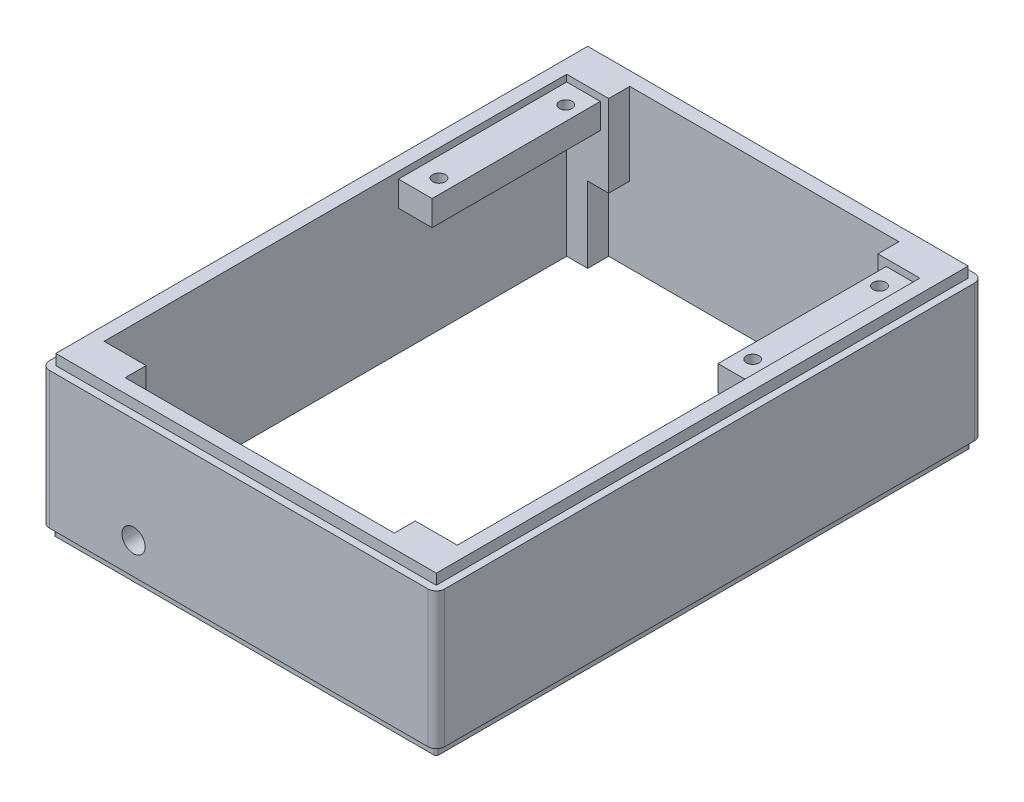
SolidWorks part; units mm, degrees
ref_plane "Front Plane" through (0, 0, 0) normal (0, 0, 1) x (1, 0, 0)
ref_plane "Top Plane" through (0, 0, 0) normal (0, 1, 0) x (1, 0, 0)
ref_plane "Right Plane" through (0, 0, 0) normal (1, 0, 0) x (0, 0, -1)
ref_plane "Plane1" through (0, 0, 0) normal (0, -1, 0) x (1, 0, 0)
sketch "Sketch1" plane through (0, 0, 0) normal (0, -1, 0) x (1, 0, 0)
  line L0 (94, 0) -> (0, 0)
  line L1 (0, 0) -> (0, -130)
  line L2 (0, -130) -> (94, -130)
  line L3 (94, -130) -> (94, 0)
extrude "Boss-Extrude1" add sketch "Sketch1" against normal blind 35
sketch "Sketch2" plane through (0, 35, 0) normal (0, 1, 0) x (-1, 0, 0)
  line L0 (-1.75, -128.25) -> (-92.25, -128.25)
  line L1 (-92.25, -128.25) -> (-92.25, -1.75)
  line L2 (-92.25, -1.75) -> (-1.75, -1.75)
  line L3 (-1.75, -1.75) -> (-1.75, -128.25)
extrude "Boss-Extrude2" add sketch "Sketch2" along normal blind 2.5
sketch "Sketch3" plane through (0, 37.5, 0) normal (0, 1, 0) x (-1, 0, 0)
  line L1 (-83, -120) -> (-79, -120)
  line L2 (-79, -120) -> (-79, -125)
  line L3 (-79, -125) -> (-15, -125)
  line L4 (-15, -125) -> (-15, -120)
  line L5 (-15, -120) -> (-5, -120)
  line L6 (-5, -120) -> (-5, -10)
  line L7 (-5, -10) -> (-15, -10)
  line L8 (-15, -10) -> (-15, -5)
  line L9 (-15, -5) -> (-79, -5)
  line L10 (-79, -5) -> (-79, -10)
  line L11 (-79, -10) -> (-89, -10)
  line L12 (-89, -10) -> (-89, -96)
  line L14 (-83, -120) -> (-89, -120)
  line L15 (-89, -120) -> (-89, -96)
extrude "Cut-Extrude1" cut sketch "Sketch3" against normal through all
sketch "Sketch4" plane through (0, 0, -10) normal (0, 0, -1) x (-1, 0, 0)
  line L0 (-15, 0) -> (-10, 0)
  line L1 (-10, 0) -> (-10, 18)
  line L2 (-10, 18) -> (-15, 18)
  line L3 (-15, 18) -> (-15, 0)
extrude "Cut-Extrude2" cut sketch "Sketch4" against normal blind 5
ref_plane "Plane2" through (0, 33.5, 0) normal (0, 1, 0) x (1, 0, 0)
ref_plane "Plane3" through (0, 31.5, 0) normal (0, -1, 0) x (1, 0, 0)
sketch "Sketch9" plane through (0, 0, -10) normal (0, 0, -1) x (-1, 0, 0)
  line L0 (-79, 18) -> (-84, 18)
  line L1 (-84, 18) -> (-84, 0)
  line L2 (-84, 0) -> (-79, 0)
  line L3 (-79, 0) -> (-79, 18)
extrude "Cut-Extrude6" cut sketch "Sketch9" against normal blind 5
sketch "Sketch11" plane through (0, 0, 0) normal (0, -1, 0) x (1, 0, 0)
  line L0 (15, -125) -> (15, -120)
  line L1 (15, -120) -> (10, -120)
  line L2 (10, -120) -> (10, -125)
  line L3 (10, -125) -> (15, -125)
extrude "Cut-Extrude8" cut sketch "Sketch11" against normal blind 18
sketch "Sketch12" plane through (0, 0, -120) normal (0, 0, 1) x (1, 0, 0)
  line L0 (79, 0) -> (84, 0)
  line L1 (84, 0) -> (84, 18)
  line L2 (84, 18) -> (79, 18)
  line L3 (79, 18) -> (79, 0)
extrude "Cut-Extrude9" cut sketch "Sketch12" against normal blind 5
hole_wizard "Ø5.5 (5.5) Diameter Hole1" positions "Sketch14" profile "Sketch13" hole size "Ø5.5" standard "ANSI Metric" end condition through all
sketch "Sketch14" plane through (0, 0, -5) normal (0, 0, -1) x (-1, 0, 0)
  point P0 (-22, 10)
sketch "Sketch13" plane through (22, 10, -5) normal (1, 0, 0) x (0, 1, 0)
  line L0 (0, 0) -> (0, 5)
  line L1 (0, 5) -> (2.75, 5)
  line L2 (2.75, 5) -> (2.75, 0)
  line L5 (2.75, 0) -> (0, 0)
  line L11 (0, -6.35) -> (0, 107.95) construction
  dimension "Thru Hole Dia." = 5.5
  dimension "Thru Hole Depth" = 5
ref_plane "Plane4" through (0, 29.5, 0) normal (0, -1, 0) x (1, 0, 0)
fillet "Fillet1" radius 2 4 edges at (0, 17.5, -130) (94, 17.5, -130) (0, 17.5, 0) (94, 17.5, 0) tangent propagation no
sketch "Sketch16" plane through (0, 0, 0) normal (0, -1, 0) x (1, 0, 0)
  line L4 (1.5, -2) -> (1.5, -128)
  line L5 (2, -128.5) -> (92, -128.5)
  line L6 (92.5, -128) -> (92.5, -2)
  line L7 (92, -1.5) -> (2, -1.5)
  line L8 (0, -2) -> (0, -128)
  line L9 (2, -130) -> (92, -130)
  line L10 (94, -128) -> (94, -2)
  line L11 (92, 0) -> (2, 0)
  line L12 (0, -2) -> (0, -128)
  line L13 (2, -130) -> (92, -130)
  line L14 (94, -128) -> (94, -2)
  line L15 (92, 0) -> (2, 0)
  arc A4 (1.5, -128) -> (2, -128.5) centre (2, -128) ccw
  arc A5 (92, -128.5) -> (92.5, -128) centre (92, -128) ccw
  arc A6 (92.5, -2) -> (92, -1.5) centre (92, -2) ccw
  arc A7 (2, -1.5) -> (1.5, -2) centre (2, -2) ccw
  arc A8 (0, -128) -> (2, -130) centre (2, -128) ccw
  arc A9 (92, -130) -> (94, -128) centre (92, -128) ccw
  arc A10 (94, -2) -> (92, 0) centre (92, -2) ccw
  arc A11 (2, 0) -> (0, -2) centre (2, -2) ccw
  arc A12 (0, -128) -> (2, -130) centre (2, -128) ccw
  arc A13 (92, -130) -> (94, -128) centre (92, -128) ccw
  arc A14 (94, -2) -> (92, 0) centre (92, -2) ccw
  arc A15 (2, 0) -> (0, -2) centre (2, -2) ccw
  dimension "D1" = 0
  dimension "D2" = 1.5
extrude "Cut-Extrude10" cut sketch "Sketch16" against normal blind 2.5
sketch "Sketch17" plane through (5, 0, 0) normal (1, 0, 0) x (0, 0, -1)
  line L0 (120, 37.5) -> (10, 37.5) construction
  line L1 (120, 35.9) -> (80, 35.9)
  line L2 (120, 35.9) -> (120, 29.9)
  line L3 (120, 29.9) -> (80, 29.9)
  line L4 (80, 35.9) -> (80, 29.9)
  line L6 (120, 0) -> (120, 37.5) construction
  dimension "D1" = 40
  dimension "D2" = 6
  dimension "D3" = 1.6
extrude "Boss-Extrude3" add sketch "Sketch17" along normal blind 8
sketch "Sketch18" plane through (89, 0, 0) normal (-1, 0, 0) x (0, 0, 1)
  line L0 (-10, 37.5) -> (-120, 37.5) construction
  line L1 (-120, 29.9) -> (-80, 29.9)
  line L2 (-120, 29.9) -> (-120, 35.9)
  line L3 (-120, 35.9) -> (-80, 35.9)
  line L4 (-80, 29.9) -> (-80, 35.9)
  line L5 (-120, 0) -> (-120, 37.5) construction
  dimension "D1" = 6
  dimension "D2" = 40
  dimension "D3" = 1.6
extrude "Boss-Extrude4" add sketch "Sketch18" along normal blind 8
sketch "Sketch23" plane through (0, 35.9, 0) normal (0, 1, 0) x (1, 0, 0)
  circle A0 centre (9.6187, 115.175) radius 1.5
  circle A1 centre (9.6187, 85.0125) radius 1.5
  circle A2 centre (84.2312, 115.175) radius 1.5
  circle A3 centre (84.2312, 85.0125) radius 1.5
  dimension "D1" = 3
  dimension "D2" = 3
  dimension "D3" = 3
  dimension "D4" = 3
extrude "Cut-Extrude11" cut sketch "Sketch23" against normal blind 4.4
ref_plane "Plane5" through (0, 0, -5) normal (0, 0, -1) x (-1, 0, 0)
ref_axis "Axis1" through (22, 10, 0) along (0, 0, -1)
ref_point "Point1"
ref_plane "Plane6" through (0, 0, 0) normal (0, 0, 1) x (1, 0, 0)
ref_point "Point2"
